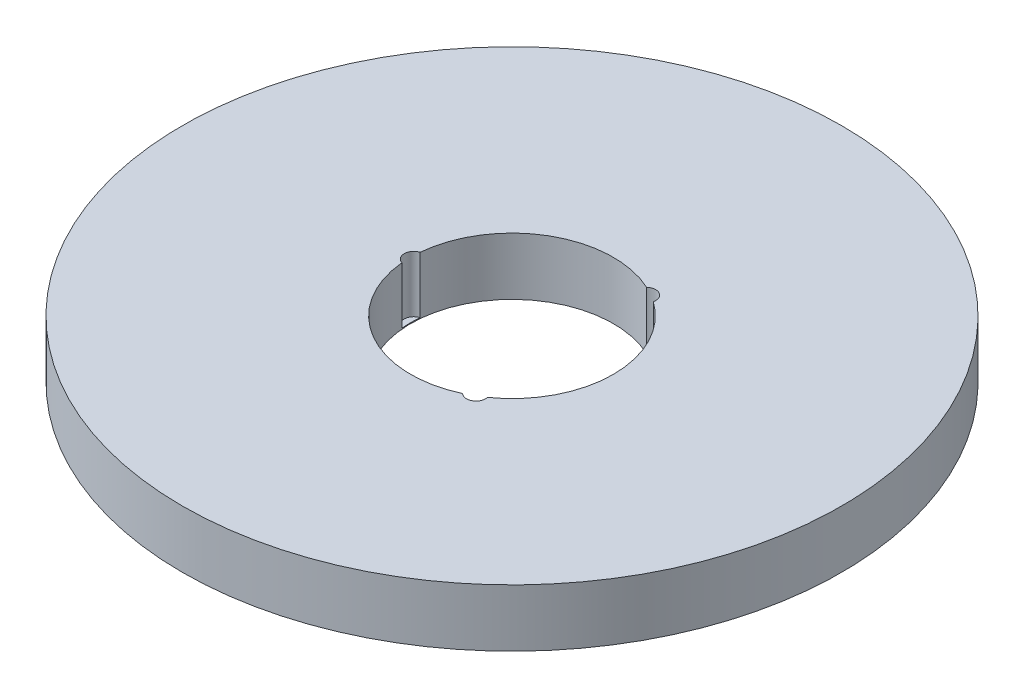
SolidWorks part; units mm, degrees
ref_plane "Front Plane" through (0, 0, 0) normal (0, 0, 1) x (1, 0, 0)
ref_plane "Top Plane" through (0, 0, 0) normal (0, 1, 0) x (1, 0, 0)
ref_plane "Right Plane" through (0, 0, 0) normal (1, 0, 0) x (0, 0, -1)
sketch "Sketch1" plane through (0, 0, 0) normal (0, 1, 0) x (1, 0, 0)
  circle A0 centre (0, 0) radius 97.5
  dimension "FLANGE_OD" = 195
extrude "Boss-Extrude1" add sketch "Sketch1" along normal blind 17
sketch "Sketch2" plane through (0, 0, 0) normal (0, 1, 0) x (1, 0, 0)
  circle A0 centre (0, 0) radius 30
  dimension "BORE_D" = 60
extrude "Cut-Extrude1" cut sketch "Sketch2" along normal through all
sketch "Sketch3" plane through (0, 17, 0) normal (0, 1, 0) x (1, 0, 0)
  circle A0 centre (0, 0) radius 29.0595 construction
  circle A1 centre (-29.0595, 0) radius 2.8173
  dimension "BOLT_D" = 5.6347
  dimension "BOLT_PCD" = 58.119
extrude "Cut-Extrude2" cut sketch "Sketch3" against normal blind 16.7506
pattern_circular "CirPattern1" count 3 over 360 about axis through (0, 0, 0) along (0, 1, 0) of "Cut-Extrude2"
